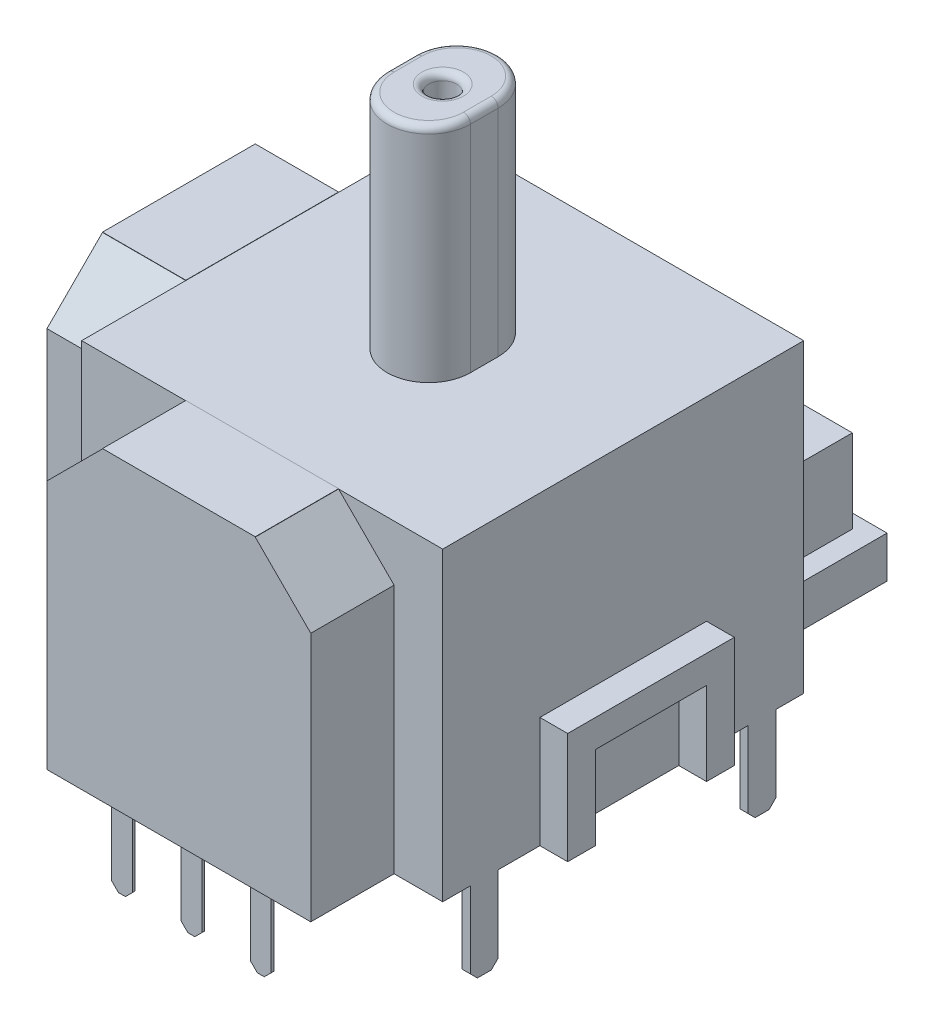
SolidWorks part; units mm, degrees
material "ABS"
ref_plane "Front" through (0, 0, 0) normal (0, 0, 1) x (1, 0, 0)
ref_plane "Top" through (0, 0, 0) normal (0, 1, 0) x (1, 0, 0)
ref_plane "Right" through (0, 0, 0) normal (1, 0, 0) x (0, 0, -1)
sketch "Sketch2" plane through (0, 0, 0) normal (1, 0, 0) x (0, 0, -1)
  line L1 (-6.5, 5.5) -> (6.5, 5.5)
  line L2 (-6.5, 5.5) -> (-6.5, -5.5)
  line L3 (-6.5, -5.5) -> (6.5, -5.5)
  line L4 (6.5, 5.5) -> (6.5, -5.5)
  line L5 (-6.5, 5.5) -> (6.5, -5.5) construction
  line L6 (-6.5, -5.5) -> (6.5, 5.5) construction
  point P0 (0, 0)
  dimension "D1" = 13
  dimension "D2" = 11
extrude "Boss-Extrude1" add sketch "Sketch2" along normal mid plane 13
sketch "Sketch3" plane through (6.5, 0, 0) normal (1, 0, 0) x (0, 0, -1)
  line L0 (-3, -1.5) -> (-3, -5.5)
  line L1 (-3, -1.5) -> (3, -1.5)
  line L2 (-3, -5.5) -> (3, -5.5)
  line L3 (3, -1.5) -> (3, -5.5)
  line L4 (-3, -1.5) -> (3, -5.5) construction
  line L5 (-3, -5.5) -> (3, -1.5) construction
  line L6 (-6.5, -5.5) -> (6.5, -5.5) construction
  line L7 (-6.5, -5.5) -> (6.5, -5.5) construction
  line L8 (-2, -2.5) -> (2, -2.5)
  line L9 (-2, -2.5) -> (-2, -5.5)
  line L10 (-2, -5.5) -> (2, -5.5)
  line L11 (2, -2.5) -> (2, -5.5)
  point P0 (0, -5.5)
  point P1 (0, -3.5)
  point P2 (0, -5.5)
  line M7 (-6.5, -5.5) -> (6.5, -5.5)
  dimension "D1" = 6
  dimension "D2" = 4
  dimension "D3" = 1
  dimension "D4" = 1
extrude "Boss-Extrude2" add sketch "Sketch3" along normal blind 1 contours L8 L11 L3 L1 L0 L9 M7 region at (6.5, -1.5721, 0)
sketch "Sketch4" plane through (0, 0, 6.5) normal (0, 0, 1) x (1, 0, 0)
  line L0 (6.5, -5.5) -> (-6.5, -5.5) construction
  line L1 (-4.75, -5.5) -> (4.75, -5.5)
  line L2 (-4.75, -5.5) -> (-4.75, 5.5)
  line L3 (-4.75, 5.5) -> (4.75, 5.5)
  line L4 (4.75, -5.5) -> (4.75, 5.5)
  line L5 (6.5, 5.5) -> (-6.5, 5.5) construction
  point P4 (0, -5.5)
  dimension "D1" = 9.5
extrude "Boss-Extrude3" add sketch "Sketch4" along normal blind 3
chamfer "Chamfer1" distance 2 angle 45 2 edges at (4.75, 5.5, 8) (-4.75, 5.5, 8)
sketch "Sketch5" plane through (-6.5, 0, 0) normal (-1, 0, 0) x (0, 0, 1)
  line L0 (6.5, -5.5) -> (-6.5, -5.5) construction
  line L1 (-4.75, 5.5) -> (4.75, 5.5)
  line L2 (-4.75, 5.5) -> (-4.75, -5.5)
  line L3 (-4.75, -5.5) -> (4.75, -5.5)
  line L4 (4.75, 5.5) -> (4.75, -5.5)
  line L5 (-6.5, 5.5) -> (6.5, 5.5) construction
  point P5 (0, -5.5)
  dimension "D1" = 9.5
extrude "Boss-Extrude4" add sketch "Sketch5" along normal blind 3
chamfer "Chamfer2" distance 2 angle 45 2 edges at (-8, 5.5, -4.75) (-8, 5.5, 4.75)
sketch "Sketch6" plane through (0, 0, -6.5) normal (0, 0, -1) x (-1, 0, 0)
  line L0 (-6.5, -5.5) -> (6.5, -5.5) construction
  line L1 (-4.5, -5.5) -> (4.5, -5.5)
  line L2 (-4.5, -5.5) -> (-4.5, -4)
  line L3 (-4.5, -4) -> (4.5, -4)
  line L4 (4.5, -5.5) -> (4.5, -4)
  point P4 (0, -5.5)
  dimension "D1" = 9
  dimension "D2" = 1.5
extrude "Boss-Extrude5" add sketch "Sketch6" along normal blind 5
sketch "Sketch7" plane through (0, 0, -6.5) normal (0, 0, -1) x (-1, 0, 0)
  line L0 (4.5, -4) -> (-4.5, -4) construction
  line L1 (-3.75, -4) -> (3.75, -4)
  line L2 (-3.75, -4) -> (-3.75, -1)
  line L3 (-3.75, -1) -> (3.75, -1)
  line L4 (3.75, -4) -> (3.75, -1)
  point P4 (0, -4)
  dimension "D1" = 3
  dimension "D2" = 7.5
extrude "Boss-Extrude6" add sketch "Sketch7" along normal blind 4.5
sketch "Sketch8" plane through (0, 5.5, 0) normal (0, 1, 0) x (1, 0, 0)
  line L0 (0, 0.5) -> (0, -0.5) construction
  line L1 (1.5, 0.5) -> (1.5, -0.5)
  line L2 (-1.5, 0.5) -> (-1.5, -0.5)
  arc A0 (1.5, 0.5) -> (-1.5, 0.5) centre (0, 0.5) ccw
  arc A1 (-1.5, -0.5) -> (1.5, -0.5) centre (0, -0.5) ccw
  circle A2 centre (0, 0) radius 0.5
  point P3 (0, 0)
  dimension "D2" = 4
  dimension "D1" = 3
extrude "Boss-Extrude7" add sketch "Sketch8" along normal blind 8
fillet "Fillet2" radius 0.25 5 edges at (0, 13.5, 0.5) (1.5, 13.5, 0) (0, 13.5, 2) (-1.5, 13.5, 0) (0, 13.5, -2)
sketch "Sketch9" plane through (0, 5.5, 0) normal (0, 1, 0) x (1, 0, 0)
  line L0 (-9.5, -2.75) -> (-6.5, -2.75) construction
  line L1 (-9.5, 2.75) -> (-6.5, 2.75)
  line L2 (-9.5, 2.75) -> (-9.5, -2.75)
  line L3 (-9.5, -2.75) -> (-6.5, -2.75)
  line L4 (-6.5, 2.75) -> (-6.5, -2.75)
  line L5 (-6.5, -2.75) -> (-6.5, -4.75) construction
  line L7 (-2.75, -6.5) -> (2.75, -6.5)
  line L8 (-2.75, -6.5) -> (-2.75, -9.5)
  line L9 (-2.75, -9.5) -> (2.75, -9.5)
  line L10 (2.75, -6.5) -> (2.75, -9.5)
extrude "Boss-Extrude8" add sketch "Sketch9" along normal blind 0.01
sketch "Sketch10" plane through (0, -5.5, 0) normal (0, -1, 0) x (1, 0, 0)
  line L0 (-6.5, -6.5) -> (-6.5, -2.75) construction
  line L1 (-6.5, -5.5) -> (-6.2, -5.5)
  line L2 (-6.5, -5.5) -> (-6.5, -4.5)
  line L3 (-6.5, -4.5) -> (-6.2, -4.5)
  line L4 (-6.2, -5.5) -> (-6.2, -4.5)
  line L5 (6.5, -6.5) -> (6.5, 6.5) construction
  line L6 (6.5, -5.5) -> (6.2, -5.5)
  line L7 (6.5, -5.5) -> (6.5, -4.5)
  line L8 (6.5, -4.5) -> (6.2, -4.5)
  line L9 (6.2, -5.5) -> (6.2, -4.5)
  line L10 (-6.5, 2.75) -> (-6.5, 6.5) construction
  line L11 (-6.5, 5.5) -> (-6.2, 5.5)
  line L12 (-6.5, 5.5) -> (-6.5, 4.5)
  line L13 (-6.5, 4.5) -> (-6.2, 4.5)
  line L14 (-6.2, 5.5) -> (-6.2, 4.5)
  line L15 (-6.5, 5) -> (-6.2, 5) construction
  line L16 (6.5, 5.5) -> (6.2, 5.5)
  line L17 (6.5, 5.5) -> (6.5, 4.5)
  line L18 (6.5, 4.5) -> (6.2, 4.5)
  line L19 (6.2, 5.5) -> (6.2, 4.5)
  line L20 (-9.2, -0.375) -> (-9.1, -0.375)
  line L21 (-6.35, -4.5) -> (-6.35, 4.5) construction
  line L22 (0, 0) -> (-6.35, 0) construction
  line L23 (-9.2, -0.375) -> (-9.2, 0.375)
  line L24 (-9.2, 0.375) -> (-9.1, 0.375)
  line L25 (-9.1, -0.375) -> (-9.1, 0.375)
  line L26 (-9.2, -0.375) -> (-9.1, 0.375) construction
  line L27 (-9.2, 0.375) -> (-9.1, -0.375) construction
  line L28 (-9.2, -2.875) -> (-9.1, -2.875)
  line L29 (-9.2, -2.875) -> (-9.2, -2.125)
  line L30 (-9.2, -2.125) -> (-9.1, -2.125)
  line L31 (-9.1, -2.875) -> (-9.1, -2.125)
  line L32 (-9.2, -2.875) -> (-9.1, -2.125) construction
  line L33 (-9.2, -2.125) -> (-9.1, -2.875) construction
  line L34 (-9.2, 2.125) -> (-9.1, 2.125)
  line L35 (-9.2, 2.125) -> (-9.2, 2.875)
  line L36 (-9.2, 2.875) -> (-9.1, 2.875)
  line L37 (-9.1, 2.125) -> (-9.1, 2.875)
  line L38 (-9.2, 2.125) -> (-9.1, 2.875) construction
  line L39 (-9.2, 2.875) -> (-9.1, 2.125) construction
  line L40 (0, 0) -> (0, 9) construction
  line L41 (-0.375, 8.95) -> (0.375, 8.95)
  line L42 (-0.375, 8.95) -> (-0.375, 9.05)
  line L43 (-0.375, 9.05) -> (0.375, 9.05)
  line L44 (0.375, 8.95) -> (0.375, 9.05)
  line L45 (-0.375, 8.95) -> (0.375, 9.05) construction
  line L46 (-0.375, 9.05) -> (0.375, 8.95) construction
  line L47 (-6.5, -5) -> (-6.2, -5) construction
  line L48 (-2.875, 8.95) -> (-2.125, 8.95)
  line L49 (-2.875, 8.95) -> (-2.875, 9.05)
  line L50 (-2.875, 9.05) -> (-2.125, 9.05)
  line L51 (-2.125, 8.95) -> (-2.125, 9.05)
  line L52 (-2.875, 8.95) -> (-2.125, 9.05) construction
  line L53 (-2.875, 9.05) -> (-2.125, 8.95) construction
  line L54 (2.125, 8.95) -> (2.875, 8.95)
  line L55 (2.125, 8.95) -> (2.125, 9.05)
  line L56 (2.125, 9.05) -> (2.875, 9.05)
  line L57 (2.875, 8.95) -> (2.875, 9.05)
  line L58 (2.125, 8.95) -> (2.875, 9.05) construction
  line L59 (2.125, 9.05) -> (2.875, 8.95) construction
  line L60 (-3.225, -5.625) -> (-2.975, -5.625)
  line L61 (-3.225, -5.625) -> (-3.225, -5.375)
  line L62 (-3.225, -5.375) -> (-2.975, -5.375)
  line L63 (-2.975, -5.625) -> (-2.975, -5.375)
  line L64 (-3.225, -5.625) -> (-2.975, -5.375) construction
  line L65 (-3.225, -5.375) -> (-2.975, -5.625) construction
  line L66 (2.775, -5.625) -> (3.025, -5.625)
  line L67 (2.775, -5.625) -> (2.775, -5.375)
  line L68 (2.775, -5.375) -> (3.025, -5.375)
  line L69 (3.025, -5.625) -> (3.025, -5.375)
  line L70 (2.775, -5.625) -> (3.025, -5.375) construction
  line L71 (2.775, -5.375) -> (3.025, -5.625) construction
  line L72 (2.775, -9.625) -> (3.025, -9.625)
  line L73 (2.775, -9.625) -> (2.775, -9.375)
  line L74 (2.775, -9.375) -> (3.025, -9.375)
  line L75 (3.025, -9.625) -> (3.025, -9.375)
  line L76 (2.775, -9.625) -> (3.025, -9.375) construction
  line L77 (2.775, -9.375) -> (3.025, -9.625) construction
  line L78 (-3.225, -9.625) -> (-2.975, -9.625)
  line L79 (-3.225, -9.625) -> (-3.225, -9.375)
  line L80 (-3.225, -9.375) -> (-2.975, -9.375)
  line L81 (-2.975, -9.625) -> (-2.975, -9.375)
  line L82 (-3.225, -9.625) -> (-2.975, -9.375) construction
  line L83 (-3.225, -9.375) -> (-2.975, -9.625) construction
  point P22 (-9.15, 0)
  point P31 (-9.15, -2.5)
  point P37 (-9.15, 2.5)
  point P42 (0, 9)
  point P47 (2.5, 9)
  point P51 (-2.5, 9)
  point P60 (2.9, -5.5)
  point P65 (2.9, -9.5)
  point P66 (-3.1, -5.5)
  point P75 (-3.1, -9.5)
  point P87 (-6.35, -5)
  dimension "D1" = 0.3
  dimension "D2" = 1
  dimension "D3" = 11
  dimension "D4" = 2.5
  dimension "D5" = 2.5
  dimension "D6" = 0.1
  dimension "D7" = 0.75
  dimension "D8" = 3
  dimension "D9" = 4
  dimension "D10" = 2.5
  dimension "D11" = 0.75
  dimension "D12" = 0.1
  dimension "D13" = 2.5
  dimension "D14" = 0.5
  dimension "D15" = 4
  dimension "D16" = 6
  dimension "D17" = 3.25
  dimension "D18" = 0.25
extrude "Boss-Extrude9" add sketch "Sketch10" along normal blind 3
chamfer "Chamfer3" distance 0.25 angle 45 20 edges at (-9.15, -8.5, 2.875) (-9.15, -8.5, 2.125) (-9.15, -8.5, 0.375) (-9.15, -8.5, -0.375) (-9.15, -8.5, -2.875) (-9.15, -8.5, -2.125) (-6.35, -8.5, 5.5) (-6.35, -8.5, 4.5) (6.35, -8.5, 5.5) (6.35, -8.5, 4.5) (6.35, -8.5, -5.5) (6.35, -8.5, -4.5) (-6.35, -8.5, -4.5) (-6.35, -8.5, -5.5) (2.875, -8.5, 9) (2.125, -8.5, 9) (0.375, -8.5, 9) (-0.375, -8.5, 9) (-2.125, -8.5, 9) (-2.875, -8.5, 9)
chamfer "Chamfer4" distance 0.1 angle 45 16 edges at (2.9, -8.5, -5.625) (2.775, -8.5, -5.5) (2.9, -8.5, -5.375) (3.025, -8.5, -5.5) (-3.1, -8.5, -5.625) (-3.225, -8.5, -5.5) (-3.1, -8.5, -5.375) (-2.975, -8.5, -5.5) (-3.1, -8.5, -9.625) (-3.225, -8.5, -9.5) (-3.1, -8.5, -9.375) (-2.975, -8.5, -9.5) (2.9, -8.5, -9.625) (2.775, -8.5, -9.5) (2.9, -8.5, -9.375) (3.025, -8.5, -9.5)
